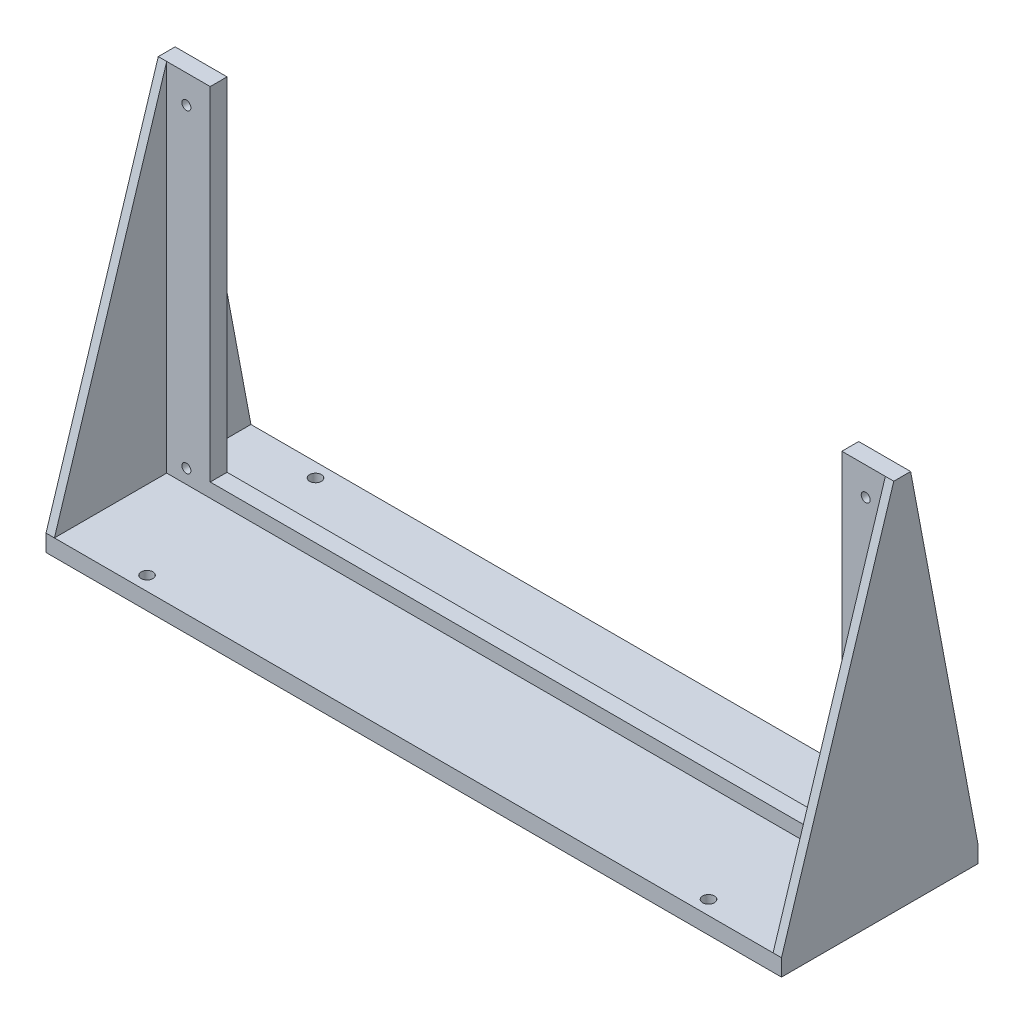
SolidWorks part; units mm, degrees
ref_plane "Front Plane" through (0, 0, 0) normal (0, 0, 1) x (1, 0, 0)
ref_plane "Top Plane" through (0, 0, 0) normal (0, 1, 0) x (1, 0, 0)
ref_plane "Right Plane" through (0, 0, 0) normal (1, 0, 0) x (0, 0, -1)
sketch "Sketch1" plane through (0, 0, 0) normal (0, 0, 1) x (1, 0, 0)
  line L1 (-121, -56) -> (121, -56) construction
  line L2 (-121, -56) -> (-121, 56) construction
  line L3 (-121, 56) -> (121, 56) construction
  line L4 (121, -56) -> (121, 56) construction
  line L5 (-121, -56) -> (121, 56) construction
  line L6 (-121, 56) -> (121, -56) construction
  line L7 (-131, -66) -> (131, -66) construction
  line L8 (-131, -66) -> (-131, 66)
  line L9 (-131, 66) -> (131, 66)
  line L10 (131, -66) -> (131, 66)
  line L11 (-131, -66) -> (131, 66) construction
  line L12 (-131, 66) -> (131, -66) construction
  line L13 (-131, -66) -> (131, -66) construction
  line L14 (-131, -66) -> (-131, -67)
  line L15 (-131, -67) -> (131, -67)
  line L16 (131, -66) -> (131, -67)
  circle A0 centre (-121, 56) radius 1.6
  circle A1 centre (121, 56) radius 1.6
  circle A2 centre (121, -56) radius 1.6
  circle A3 centre (-121, -56) radius 1.6
  point P0 (0, 0)
  point P6 (0, 0)
  dimension "D1" = 3.2
  dimension "D2" = 242
  dimension "D3" = 112
  dimension "D4" = 10
  dimension "D5" = 10
  dimension "D6" = 1
extrude "Boss-Extrude1" add sketch "Sketch1" along normal blind 6
sketch "Sketch5" plane through (0, 0, 6) normal (0, 0, 1) x (1, 0, 0)
  line L0 (131, -67) -> (131, 66) construction
  line L1 (-131, -67) -> (131, -67)
  line L2 (-131, -67) -> (-131, -61)
  line L3 (-131, -61) -> (131, -61)
  line L4 (131, -67) -> (131, -61)
  dimension "D1" = 6
extrude "Boss-Extrude3" add sketch "Sketch5" along normal blind 40
extrude "Boss-Extrude5" add sketch "Sketch5<2>" against normal blind 30
sketch "Sketch5<2>" plane through (0, 0, 6) normal (0, 0, 1) x (1, 0, 0) same geometry as "Sketch5"
sketch "Sketch3" plane through (0, -61, 0) normal (0, 1, 0) x (1, 0, 0)
  line L0 (-131, -41) -> (131, -41) construction
  line L1 (-131, 19) -> (131, 19) construction
  line L2 (-131, 24) -> (-131, 0) construction
  line L3 (131, 24) -> (131, 0) construction
  line L4 (131, 24) -> (-131, 24) construction
  line L5 (131, -46) -> (-131, -46) construction
  line L6 (-131, -46) -> (-131, -6) construction
  line L7 (131, -46) -> (131, -6) construction
  line L8 (-100, -41) -> (100, -41) construction
  line L10 (-100, -41) -> (100, -41) construction
  line L11 (-100, -41) -> (-100, 19) construction
  line L12 (-100, 19) -> (100, 19) construction
  line L13 (100, -41) -> (100, 19) construction
  circle A0 centre (-100, -41) radius 2.1
  circle A1 centre (100, -41) radius 2.1
  circle A2 centre (-100, 19) radius 2.1
  circle A3 centre (100, 19) radius 2.1
  point P22 (0, -41)
  dimension "D1" = 4.2
  dimension "D2" = 200
  dimension "D3" = 5
  dimension "D4" = 5
extrude "Cut-Extrude1" cut sketch "Sketch3" against normal through all
sketch "Sketch6" plane through (0, 0, 6) normal (0, 0, 1) x (1, 0, 0)
  line L0 (0, 66) -> (0, -67) construction
  line L1 (131, 66) -> (-131, 66) construction
  line L2 (-131, -67) -> (131, -67) construction
  line L3 (131, -61) -> (-131, -61) construction
  line L4 (-112.5, -56) -> (112.5, -56)
  line L5 (-112.5, -56) -> (-112.5, 66)
  line L6 (-112.5, 66) -> (112.5, 66)
  line L7 (112.5, -56) -> (112.5, 66)
  line L8 (-112.5, -56) -> (112.5, 66) construction
  line L9 (-112.5, 66) -> (112.5, -56) construction
  point P6 (0, 5)
  point P18 (121, 56)
  dimension "D1" = 225
  dimension "D2" = 5
extrude "Cut-Extrude2" cut sketch "Sketch6" against normal through all
sketch "Sketch7" plane through (-131, 0, 0) normal (-1, 0, 0) x (0, 0, 1)
  line L0 (6, 66) -> (46, -61)
  line L1 (6, 66) -> (6, -61)
  line L2 (6, -61) -> (46, -61)
  line L3 (0, 66) -> (-24, -61)
  line L4 (-24, -61) -> (0, -61)
  line L5 (0, -61) -> (0, 66)
  line L6 (0, 66) -> (0, -61) construction
  point P10 (0, 0)
  point P13 (0, 0)
  point P14 (0, -61)
  point P17 (-24, -61)
sketch "Sketch8" plane through (131, 0, 0) normal (1, 0, 0) x (0, 0, -1)
  line L0 (-6, 66) -> (-46, -61)
  line L1 (-6, 66) -> (-6, -61)
  line L2 (-6, -61) -> (-46, -61)
  line L3 (0, 66) -> (0, -61)
  line L4 (0, -61) -> (24, -61)
  line L5 (24, -61) -> (0, 66)
  line L6 (24, -67) -> (24, -61) construction
  line L7 (24, -61) -> (0, -61) construction
  point P10 (0, 0)
  point P13 (24, -61)
  point P18 (0, 0)
  point P19 (0, 0)
extrude "Boss-Extrude4" add sketch "Sketch8" against normal blind 3
extrude "Boss-Extrude6" add sketch "Sketch7" against normal blind 3
